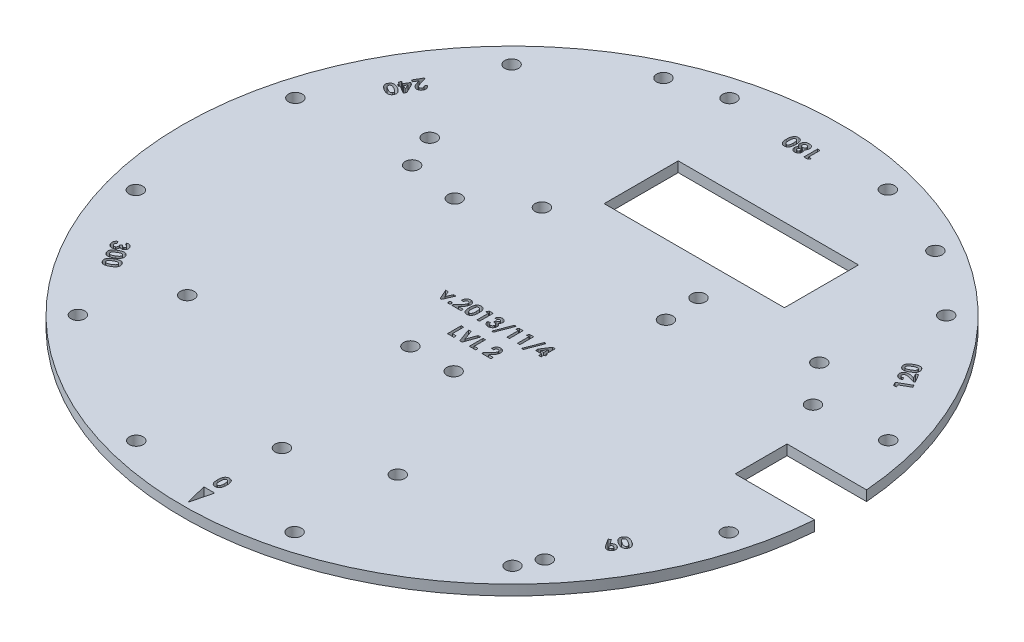
SolidWorks part; units mm, degrees
ref_plane "Front" through (0, 0, 0) normal (0, 0, 1) x (1, 0, 0)
ref_plane "Top" through (0, 0, 0) normal (0, 1, 0) x (1, 0, 0)
ref_plane "Right" through (0, 0, 0) normal (1, 0, 0) x (0, 0, -1)
sketch "Sketch1" plane through (0, 0, 0) normal (0, 1, 0) x (1, 0, 0)
  circle A3 centre (0, 0) radius 76.2
  point P18 (0, 0)
  dimension "D1" = 152.4
extrude "Boss-Extrude1" add sketch "Sketch1" along normal blind 1 and the other way blind 1.3622
sketch "Sketch10" plane through (0, 1, 0) normal (0, 1, 0) x (1, 0, 0)
  line L0 (-5.5, -18) -> (4.5, -18) construction
  circle A0 centre (-5.5, -18) radius 1.59
  circle A5 centre (4.5, -18) radius 1.59
  dimension "D1" = 10
  dimension "D4" = 3.18
  dimension "D2" = 18
  dimension "D3" = 4.5
extrude "Camera Mount Holes" cut sketch "Sketch10" against normal through all
sketch "Sketch13" plane through (0, 1, 0) normal (0, 1, 0) x (1, 0, 0)
  line L0 (18.7192, 16.8564) -> (18.7192, -45.1436) construction
  line L1 (18.7192, -45.1436) -> (52.7192, -45.1436) construction
  line L2 (52.7192, -45.1436) -> (52.7192, 16.8564) construction
  line L3 (52.7192, 16.8564) -> (18.7192, 16.8564) construction
  circle A0 centre (18.7192, -45.1436) radius 1.59
  circle A1 centre (52.7192, 16.8564) radius 1.59
  circle A2 centre (52.7192, -45.1436) radius 1.59
  circle A3 centre (18.7192, 16.8564) radius 1.59
  dimension "D1" = 62
  dimension "D2" = 16.8564
  dimension "D5" = 3.18
  dimension "D4" = 34
  dimension "D3" = 45.1436
  dimension "D6" = 18.7192
extrude "Power Board Mounting Holes" cut sketch "Sketch13" against normal blind 10
sketch "Sketch15" plane through (0, 1, 0) normal (0, 1, 0) x (1, 0, 0)
  line L0 (0, 78.944) -> (0, -96.9952) construction
  line L1 (-154.9483, 0) -> (164.5667, 0) construction
  line L2 (0, 0) -> (-45.0333, 26) construction
  line L3 (0, 0) -> (45.0333, 26) construction
  circle A0 centre (-45.0333, 26) radius 1.59
  circle A1 centre (45.0333, 26) radius 1.59
  circle A2 centre (0, -53.21) radius 1.59
  dimension "D1" = 30
  dimension "D4" = 52
  dimension "D5" = 3.18
  dimension "D6" = 53.21
  dimension "D2" = 30
  dimension "D3" = 52
extrude "Structure Mounting Holes" cut sketch "Sketch15" against normal through all
sketch "Sketch11" plane through (0, 1, 0) normal (0, 1, 0) x (1, 0, 0)
  line L4 (-29.9736, 16.7231) -> (-29.9736, 64.9831) construction
  line L5 (-29.9736, 64.9831) -> (36.0664, 64.9831) construction
  line L6 (36.0664, 64.9831) -> (36.0664, 61.8081) construction
  circle A0 centre (-29.9736, 16.7231) radius 1.59
  circle A1 centre (-29.9736, 64.9831) radius 1.59
  circle A2 centre (36.0664, 61.8081) radius 1.59
  dimension "D1" = 29.9736
  dimension "D5" = 48.26
  dimension "D8" = 3.18
  dimension "D2" = 16.7231
  dimension "D6" = 66.04
  dimension "D7" = 3.175
extrude "BeagleBone Mounting Holes" cut sketch "Sketch11" against normal blind 10
sketch "Sketch17" plane through (0, 1, 0) normal (0, 1, 0) x (1, 0, 0)
  line L0 (0, 0) -> (0, 50000) construction
  line L1 (0, 0) -> (-50000, 0) construction
  line L2 (0, 0) -> (50.242, 50.1383) construction
  line L3 (-1.25, -70) -> (1.25, -70)
  line L4 (1.25, -70) -> (0, -75)
  line L5 (0, -75) -> (-1.25, -70)
  circle A0 centre (-18.3, 68.58) radius 1.59
  circle A1 centre (18.3, 68.58) radius 1.59
  circle A2 centre (50.242, 50.1383) radius 1.59
  circle A3 centre (68.542, 18.4417) radius 1.59
  circle A4 centre (68.542, -18.4417) radius 1.59
  circle A5 centre (50.242, -50.1383) radius 1.59
  circle A6 centre (18.3, -68.58) radius 1.59
  circle A7 centre (-18.3, -68.58) radius 1.59
  circle A8 centre (-50.242, -50.1383) radius 1.59
  circle A9 centre (-68.542, -18.4417) radius 1.59
  circle A10 centre (-68.542, 18.4417) radius 1.59
  circle A11 centre (-50.242, 50.1383) radius 1.59
  point P32 (0, 0)
  dimension "D1" = 68.58
  dimension "D3" = 3.18
  dimension "D5" = 44.941
  dimension "D2" = 36.6
  dimension "D6" = 70.9796
  dimension "D7" = 2.5
  dimension "D8" = 5
  dimension "D9" = 70
  dimension "D4" = 6
extrude "DMS Sensor Mounting Holes" cut sketch "Sketch17" against normal up to surface (2.3622 mm away) up to face at (36.0664, -1.3622, -60.2181)
sketch "Sketch12" plane through (0, 1, 0) normal (0, 1, 0) x (1, 0, 0)
  line L0 (-68.542, 18.4417) -> (-68.542, -33.5583) construction
  line L3 (0, 113.7141) -> (0, -131.2105) construction
  line L4 (113.7835, 0) -> (-132.552, 0) construction
  line L5 (-68.542, -33.5583) -> (-41.542, -33.5583) construction
  line L6 (-41.542, -33.5583) -> (-41.542, 18.4417) construction
  line L7 (-41.542, 18.4417) -> (-68.542, 18.4417) construction
  circle A1 centre (-41.542, 18.4417) radius 1.59
  circle A3 centre (-41.542, -33.5583) radius 1.59
  dimension "D3" = 3.18
  dimension "D2" = 27
  dimension "D1" = 52
extrude "Peripheral Board Mounting Holes" cut sketch "Sketch12" against normal through all
sketch "Sketch14" plane through (0, 1, 0) normal (0, 1, 0) x (1, 0, 0)
  line L1 (-11.6792, 32.9727) -> (30, 32.9727)
  line L3 (30, 32.9727) -> (30, 50.1004)
  line L7 (30, 50.1004) -> (-11.6792, 50.1004)
  line L8 (-11.6792, 32.9727) -> (-11.6792, 50.1004)
  line L13 (57.5816, 6) -> (57.5816, -6)
  line L14 (57.5816, -6) -> (75.9634, -6)
  line L18 (57.5816, 6) -> (75.9634, 6)
  arc A0 (75.9634, 6) -> (75.9634, -6) centre (75.9634, 0) cw
  circle A1 centre (18.1, 25) radius 1.59
  circle A3 centre (0, 0) radius 76.2 construction
  circle A8 centre (-18.1, 25) radius 1.59
  dimension "D2" = 3.18
  dimension "D4" = 57.5816
  dimension "D7" = 36.2
  dimension "D6" = 18.1
  dimension "D10" = 11.6792
  dimension "D8" = 25
  dimension "D9" = 25
  dimension "D1" = 6
  dimension "D3" = 41.6792
  dimension "D5" = 17.1277
  dimension "D11" = 32.9727
extrude "DMS Board and Wire Holes" cut sketch "Sketch14" against normal blind 2.5
sketch "Sketch18" plane through (0, 1, 0) normal (0, 1, 0) x (1, 0, 0)
  line L0 (-18.3, -68.58) -> (18.3, -68.58) construction
  line L1 (68.542, -18.4417) -> (50.242, -50.1383) construction
  line L2 (50.242, 50.1383) -> (68.542, 18.4417) construction
  line L3 (18.3, 68.58) -> (-18.3, 68.58) construction
  line L4 (-50.242, 50.1383) -> (-68.542, 18.4417) construction
  line L5 (-68.542, -18.4417) -> (-50.242, -50.1383) construction
  line L6 (-20, -5) -> (20, -5) construction
  text T0 "<b>              0</b>"
  text T1 "<b>            300</b>"
  text T2 "<b>            240</b>"
  text T3 "<b>60             </b>"
  text T4 "<b>120            </b>"
  text T5 "<b>            180</b>"
  text T6 "<b>      v.2013/11/4</b>\r\n<b>             LVL 2</b>"
  dimension "D1" = 5
  dimension "D2" = 40
  dimension "D3" = 20
extrude "Cut-Extrude10" cut sketch "Sketch18" against normal up to surface (2.3622 mm away) up to face at (-18.1, -1.3622, -23.41)
